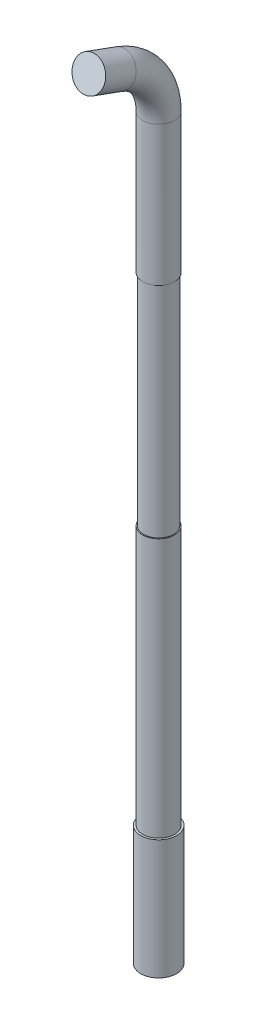
SolidWorks part; units mm, degrees
material "Stainless Steel (ferritic)"
ref_plane "Front Plane" through (0, 0, 0) normal (0, 0, 1) x (1, 0, 0)
ref_plane "Top Plane" through (0, 0, 0) normal (0, 1, 0) x (1, 0, 0)
ref_plane "Right Plane" through (0, 0, 0) normal (1, 0, 0) x (0, 0, -1)
sketch "Sketch1" plane through (0, 0, 0) normal (1, 0, 0) x (0, 0, -1)
  line L0 (9, 0) -> (9, 37)
  line L1 (55, 0) -> (-55, 0) construction
  line L2 (7.0261, 39.8191) -> (5.5, 40.3745)
  line L4 (0, 55) -> (0, -55) construction
  arc A0 (9, 37) -> (7.0261, 39.8191) centre (6, 37) ccw
  dimension "D1" = 3
  dimension "D2" = 9
  dimension "D3" = 37
  dimension "D4" = 3.5
  dimension "D5" = 70
sketch "Sketch2" plane through (0, 0, 0) normal (0, 1, 0) x (1, 0, 0)
  circle A0 centre (0, 9) radius 0.8
  dimension "D1" = 1.6
sweep "Sweep1" add profiles "Sketch2" path "Sketch1"
sketch "Sketch4" plane through (0, 0, 0) normal (0, 1, 0) x (1, 0, 0)
  circle A0 centre (0, 9) radius 0.9
  dimension "D1" = 1.8
extrude "Extrude1" add sketch "Sketch4" along normal blind 6
ref_plane "Plane1" through (0, 19, 0) normal (0, 1, 0) x (-1, 0, 0)
sketch "Sketch5" plane through (0, 19, 0) normal (0, 1, 0) x (-1, 0, 0)
  circle A0 centre (0, -9) radius 0.75
  dimension "D1" = 1.5
extrude "Extrude3" cut sketch "Sketch5" along normal blind 11 flip side to cut
ref_axis "Axis1" through (0, 37, -9) along (0, -1, 0)
